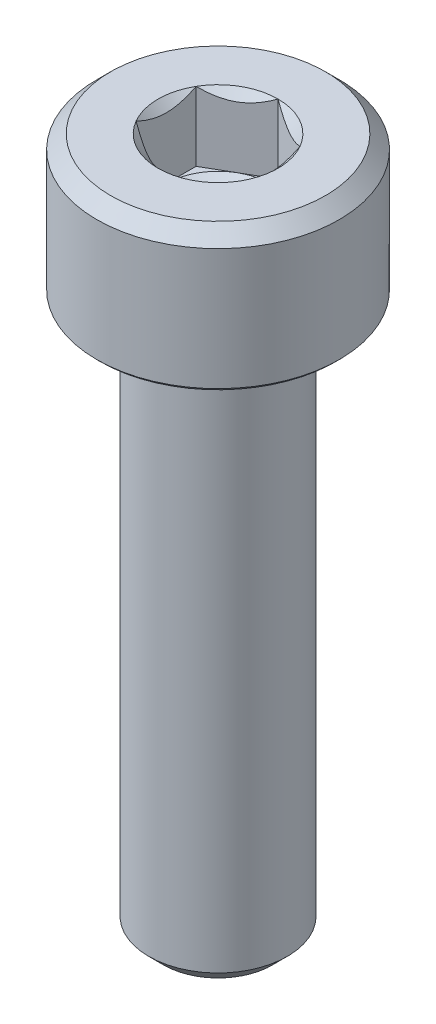
SolidWorks part; units mm, degrees
ref_plane "Front Plane" through (0, 0, 0) normal (0, 0, 1) x (1, 0, 0)
ref_plane "Top Plane" through (0, 0, 0) normal (0, 1, 0) x (1, 0, 0)
ref_plane "Right Plane" through (0, 0, 0) normal (1, 0, 0) x (0, 0, -1)
sketch "Sketch1" plane through (0, 0, 0) normal (0, 0, 1) x (1, 0, 0)
  line L0 (0, 1.134) -> (1.5, 2)
  line L1 (1.5, 2) -> (1.5, 3.7679)
  line L2 (1.5, 3.7679) -> (1.7321, 4)
  line L3 (1.7321, 4) -> (3.1, 4)
  line L4 (3.1, 4) -> (3.5, 3.6)
  line L5 (3.5, 3.6) -> (3.5, 0.1)
  line L6 (3.5, 0.1) -> (3.4, 0)
  line L7 (3.4, 0) -> (2.05, 0)
  line L8 (2.05, 0) -> (2, -0.6)
  line L9 (2, -0.6) -> (2, -15.5705)
  line L10 (2, -15.5705) -> (1.5705, -16)
  line L11 (1.5705, -16) -> (0, -16)
  line L12 (0, -16) -> (0, 1.134)
  line L13 (0, -16) -> (0, 4) construction
revolve "Revolve1" add sketch "Sketch1" angle 360 about L13 reverse direction yes
cosmetic thread "Cosmetic Thread1" parameters "D1"=13.9, "D2"=3.141
ref_plane "Plane1" through (0, 4, 0) normal (0, 1, 0) x (1, 0, 0)
sketch "Sketch2" plane through (0, 4, 0) normal (0, 1, 0) x (1, 0, 0)
  line L0 (-1.5, -0.866) -> (0, -1.7321)
  line L1 (0, -1.7321) -> (1.5, -0.866)
  line L2 (1.5, -0.866) -> (1.5, 0.866)
  line L3 (1.5, 0.866) -> (0, 1.7321)
  line L4 (0, 1.7321) -> (-1.5, 0.866)
  line L5 (-1.5, 0.866) -> (-1.5, -0.866)
extrude "Cut-Extrude1" cut sketch "Sketch2" against normal blind 2
ref_plane "Plane2" through (0, -16, 0) normal (0, 1, 0) x (1, 0, 0)
ref_plane "ANBAU XY" through (0, 0, 0) normal (0, 1, 0) x (1, 0, 0)
ref_plane "ANBAU XZ" through (0, 0, 0) normal (0, 0, 1) x (1, 0, 0)
ref_plane "ANBAU YZ" through (0, 0, 0) normal (1, 0, 0) x (0, 0, -1)
ref_axis "ANBAU X" through (-80.9, 0, 0) along (1, 0, 0)
ref_axis "ANBAU Y" through (0, 0, 50) along (0, 0, -1)
ref_axis "ANBAU Z" through (0, 50, 0) along (0, -1, 0)
sketch3d "ANBAU"
  point P0 (0, 0, 0)
ref_plane "Schraube XY" through (0, 0, 0) normal (0, 1, 0) x (1, 0, 0)
ref_plane "Schraube XZ" through (0, 0, 0) normal (0, 0, 1) x (1, 0, 0)
ref_plane "Schraube YZ" through (0, 0, 0) normal (1, 0, 0) x (0, 0, -1)
ref_axis "Schraube X" through (-80.9, 0, 0) along (1, 0, 0)
ref_axis "Schraube Y" through (0, 0, 50) along (0, 0, -1)
ref_axis "Schraube Z" through (0, 50, 0) along (0, -1, 0)
sketch3d "Schraube"
  point P0 (0, 0, 0)
ref_plane "insert XY" through (0, 0, 0) normal (0, 1, 0) x (1, 0, 0)
ref_plane "insert XZ" through (0, 0, 0) normal (0, 0, 1) x (1, 0, 0)
ref_plane "insert YZ" through (0, 0, 0) normal (1, 0, 0) x (0, 0, -1)
ref_axis "insert X" through (-80.9, 0, 0) along (1, 0, 0)
ref_axis "insert Y" through (0, 0, 50) along (0, 0, -1)
ref_axis "insert Z" through (0, 50, 0) along (0, -1, 0)
sketch3d "insert"
  point P0 (0, 0, 0)
ref_plane "schrauben_punkt XY" through (0, -16, 0) normal (0, 1, 0) x (1, 0, 0)
ref_plane "schrauben_punkt XZ" through (0, 0, 0) normal (0, 0, 1) x (1, 0, 0)
ref_plane "schrauben_punkt YZ" through (0, 0, 0) normal (1, 0, 0) x (0, 0, -1)
ref_axis "schrauben_punkt X" through (-80.9, -16, 0) along (1, 0, 0)
ref_axis "schrauben_punkt Y" through (0, -16, 50) along (0, 0, -1)
ref_axis "schrauben_punkt Z" through (0, 50, 0) along (0, -1, 0)
sketch3d "schrauben_punkt"
  point P0 (0, -16, 0)
other "Freeze***"
